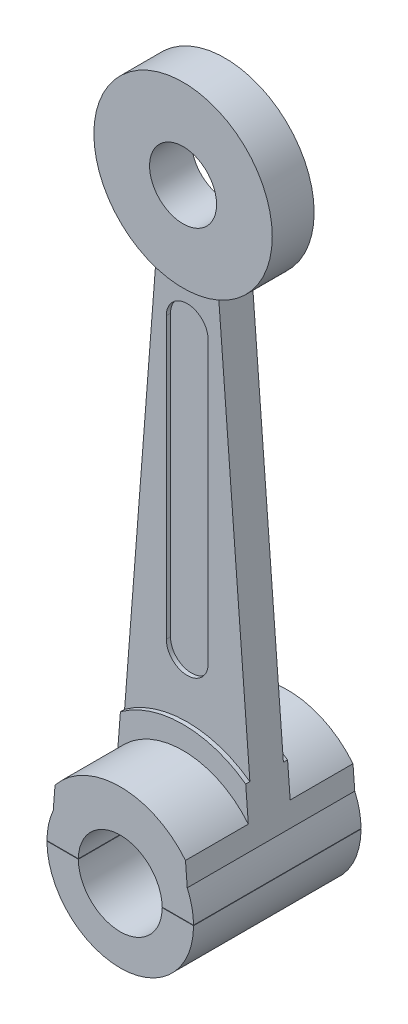
SolidWorks part; units mm, degrees
ref_plane "Front Plane" through (0, 0, 0) normal (0, 0, 1) x (1, 0, 0)
ref_plane "Top Plane" through (0, 0, 0) normal (0, 1, 0) x (1, 0, 0)
ref_plane "Right Plane" through (0, 0, 0) normal (1, 0, 0) x (0, 0, -1)
sketch "Sketch2" plane through (0, 0, 0) normal (0, 0, 1) x (1, 0, 0)
  line L0 (0, 0) -> (0, 13.69) construction
  line L1 (-0.75, 11.6964) -> (-1.65, 1.9311)
  line L2 (0.75, 11.6964) -> (1.65, 1.9311)
  line L3 (0, 10.69) -> (0, 4) construction
  line L4 (0.5, 10.69) -> (0.5, 4)
  line L5 (-0.5, 10.69) -> (-0.5, 4)
  circle A0 centre (0, 0) radius 2.54
  circle A1 centre (0, 0) radius 1
  circle A2 centre (0, 13.69) radius 0.8
  circle A3 centre (0, 13.69) radius 2.13
  arc A4 (0.5, 10.69) -> (-0.5, 10.69) centre (0, 10.69) ccw
  arc A5 (-0.5, 4) -> (0.5, 4) centre (0, 4) ccw
  point P13 (0, 7.345)
  dimension "D1" = 5.08
  dimension "D2" = 2
  dimension "D3" = 4.26
  dimension "D4" = 1.6
  dimension "D7" = 0.5
  dimension "D8" = 3
  dimension "D9" = 4
  dimension "D5" = 13.69
  dimension "D6" = 1.5
  dimension "D10" = 3.3
extrude "Boss-Extrude1" add sketch "Sketch2" along normal mid plane 1 contours A3 A2 | A0 A1 region at (-1.178, 15.3918, 0) region at (0, 2.4682, 0)
extrude "Boss-Extrude2" add sketch "Sketch2<3>" along normal mid plane 0.8 contours A3 L1 A0 L2 A5 L5 A4 L4 region at (0, 11.4569, 0)
sketch "Sketch2<3>" plane through (0, 0, 0) normal (0, 0, 1) x (1, 0, 0) same geometry as "Sketch2"
extrude "Boss-Extrude3" add sketch "Sketch2<4>" along normal mid plane 0.6 contours L5 A5 L4 A4 region at (0, 7.345, 0)
sketch "Sketch2<4>" plane through (0, 0, 0) normal (0, 0, 1) x (1, 0, 0) same geometry as "Sketch2"
sketch "Sketch3" plane through (0, 0, 0.5) normal (0, 0, 1) x (1, 0, 0)
  circle A0 centre (0, 0) radius 1
  circle A1 centre (0, 0) radius 2
  dimension "D1" = 4
  dimension "D2" = 2
extrude "Boss-Extrude5" add sketch "Sketch3" along normal blind 1.5 and the other way blind 2.5
sketch "Sketch4" plane through (0, 0, 0) normal (0, 0, 1) x (1, 0, 0)
  line L0 (-0.75, 11.6964) -> (-2.9029, 1.9553)
  line L1 (0.75, 11.6964) -> (2.9029, 1.9553)
  line L2 (-1.6, 0.7089) -> (-0.75, 11.6964)
  line L3 (0.75, 11.6964) -> (1.6, 0.7089)
  arc A0 (-1.6, 0.7089) -> (1.6, 0.7089) centre (0, 0) ccw
  arc A1 (-2.9029, 1.9553) -> (2.9029, 1.9553) centre (0, 0) ccw
  dimension "D2" = 1.75
  dimension "D3" = 3.5
  dimension "D1" = 3.2
extrude "Cut-Extrude1" cut sketch "Sketch4" against normal mid plane 61.5
sketch "Sketch5" plane through (0, 0, 0) normal (0, 0, 1) x (1, 0, 0)
  line L0 (0, 0) -> (4.0992, 0) construction
  line L2 (4.0992, 0) -> (-4.1819, 0)
  line L3 (4.0992, 0) -> (4.0992, 0.01)
  line L4 (4.0992, 0.01) -> (-4.1819, 0.01)
  line L5 (-4.1819, 0) -> (-4.1819, 0.01)
  line L6 (4.0992, 0) -> (-4.1819, 0.01) construction
  line L7 (4.0992, 0.01) -> (-4.1819, 0) construction
  point P6 (-0.0414, 0.005)
  dimension "D1" = 0.01
extrude "Cut-Extrude2" cut sketch "Sketch5" against normal mid plane 61.5
